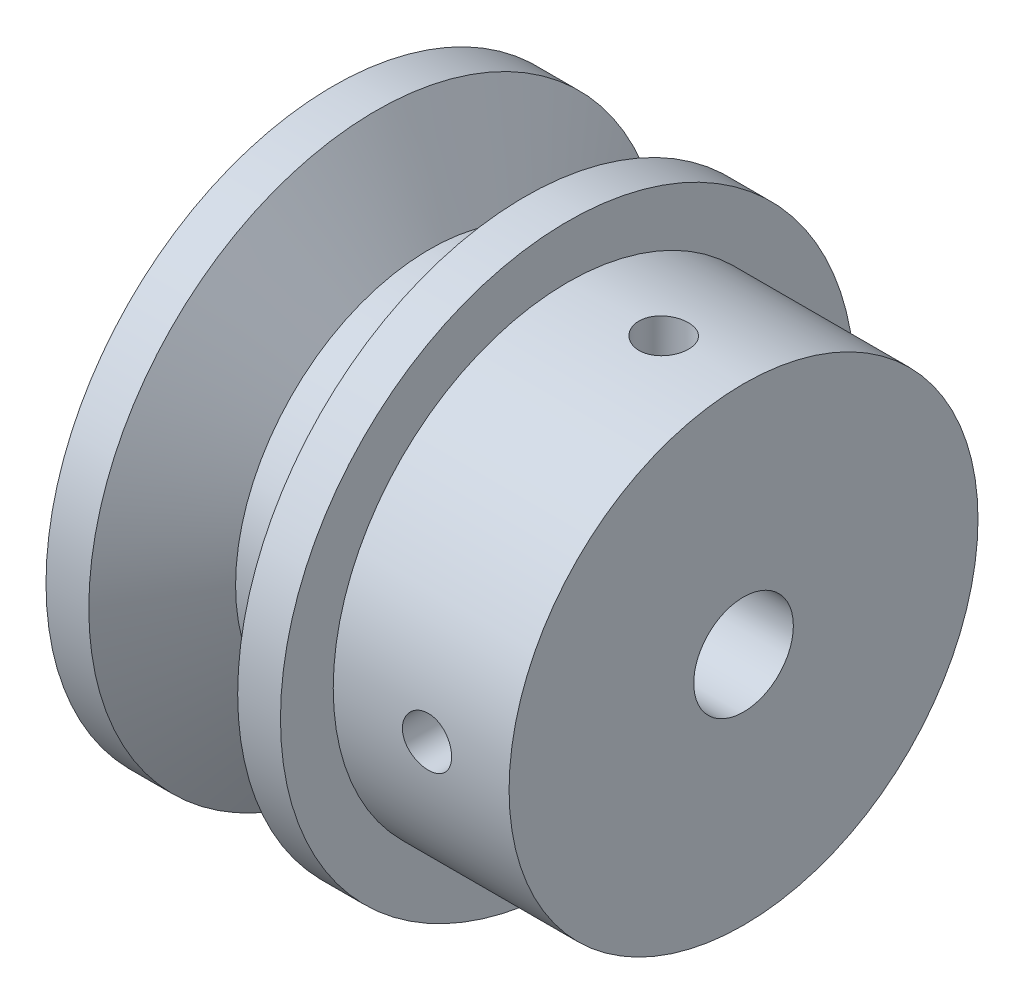
SolidWorks part; units mm, degrees
material "Aleación 1060"
ref_plane "Front" through (0, 0, 0) normal (0, 0, 1) x (1, 0, 0)
ref_plane "Top" through (0, 0, 0) normal (0, 1, 0) x (1, 0, 0)
ref_plane "Right" through (0, 0, 0) normal (1, 0, 0) x (0, 0, -1)
sketch "Croquis1" plane through (0, 0, 0) normal (0, 0, 1) x (1, 0, 0)
  line L0 (0, 0) -> (35, 0)
  line L1 (35, 0) -> (35, 20)
  line L2 (35, 20) -> (20, 20)
  line L3 (20, 20) -> (20, 24.5)
  line L5 (0, 24.5) -> (0, 0)
  line L6 (0, 24.5) -> (3.65, 24.5)
  line L9 (8.2327, 16.5625) -> (11.7673, 16.5625)
  line L11 (3.65, 24.5) -> (12.9824, 18.6672) construction
  line L12 (7.0176, 18.6672) -> (16.35, 24.5) construction
  line L13 (16.35, 24.5) -> (20, 24.5)
  line L14 (3.65, 24.5) -> (8.2327, 16.5625)
  line L15 (8.2327, 16.5625) -> (10, 16.5625)
  line L16 (10, 16.5625) -> (10, 20.5312) construction
  line L17 (16.35, 24.5) -> (11.7673, 16.5625)
  point P11 (10, 20.5312)
  dimension "D1" = 24.5
  dimension "D2" = 20
  dimension "D3" = 15
  dimension "D4" = 20
  dimension "D5" = 12.7
  dimension "D6" = 60
revolve "Revolución1" add sketch "Croquis1" angle 360 about L0 region at (17.2357, 10.518, 0)
sketch "Croquis2" plane through (35, 0, 0) normal (1, 0, 0) x (0, 0, -1)
  circle A0 centre (0, 0) radius 5
  dimension "D1" = 10
extrude "Cortar-Extruir1" [suppressed] cut sketch "Croquis2" against normal up to surface (35 mm away) up to face at (0, 0, 24.5)
hole_wizard "Perforador para roscar para macho de roscar para M51" positions "Croquis3D1" profile "Croquis3" hole size "M5" standard "ISO"
sketch3d "Croquis3D1"
  line L1 (28, 19.9991, -0.1929) -> (0, 0, 0) construction
  line L4 (0, 0, 0) -> (0, 0, 20) construction
  point P4 (28, 0, 20)
  point P6 (28, 19.9991, -0.1929)
  dimension "D1" = 7
  dimension "D2" = 7
cosmetic thread "Rosca cosmética1" parameters "D2"=5
cosmetic thread "Rosca cosmética2" parameters "D2"=5
sketch "Croquis3" plane through (28, 0, 20) normal (1, 0, 0) x (0, -1, 0)
  line L0 (0, 0) -> (0, 21.2618)
  line L1 (0, 21.2618) -> (2.1, 20)
  line L2 (2.1, 20) -> (2.1, 0)
  line L5 (2.1, 0) -> (0, 0)
  line L10 (0, 21.2618) -> (-2.1, 20) construction
  line L11 (0, -6.35) -> (0, 107.95) construction
  dimension "Diámetro de taladro" = 4.2
  dimension "Profundidad de taladro" = 20
  dimension "Ángulo de perforador" = 118
hole_wizard "Perforador para roscar para macho de roscar para M101" positions "Croquis4" profile "Croquis5" hole size "M10" standard "ISO"
sketch "Croquis4" plane through (35, 0, 0) normal (1, 0, 0) x (0, 0, -1)
  point P0 (0, 0)
sketch "Croquis5" plane through (35, 0, 0) normal (0, 1, 0) x (0, 0, -1)
  line L0 (0, 0) -> (0, 42.5537)
  line L1 (0, 42.5537) -> (4.25, 40)
  line L2 (4.25, 40) -> (4.25, 0)
  line L5 (4.25, 0) -> (0, 0)
  line L10 (0, 42.5537) -> (-4.25, 40) construction
  line L11 (0, -6.35) -> (0, 107.95) construction
  dimension "Diámetro de taladro" = 8.5
  dimension "Profundidad de taladro" = 40
  dimension "Ángulo de perforador" = 118
cosmetic thread "Rosca cosmética3" parameters "D2"=10
